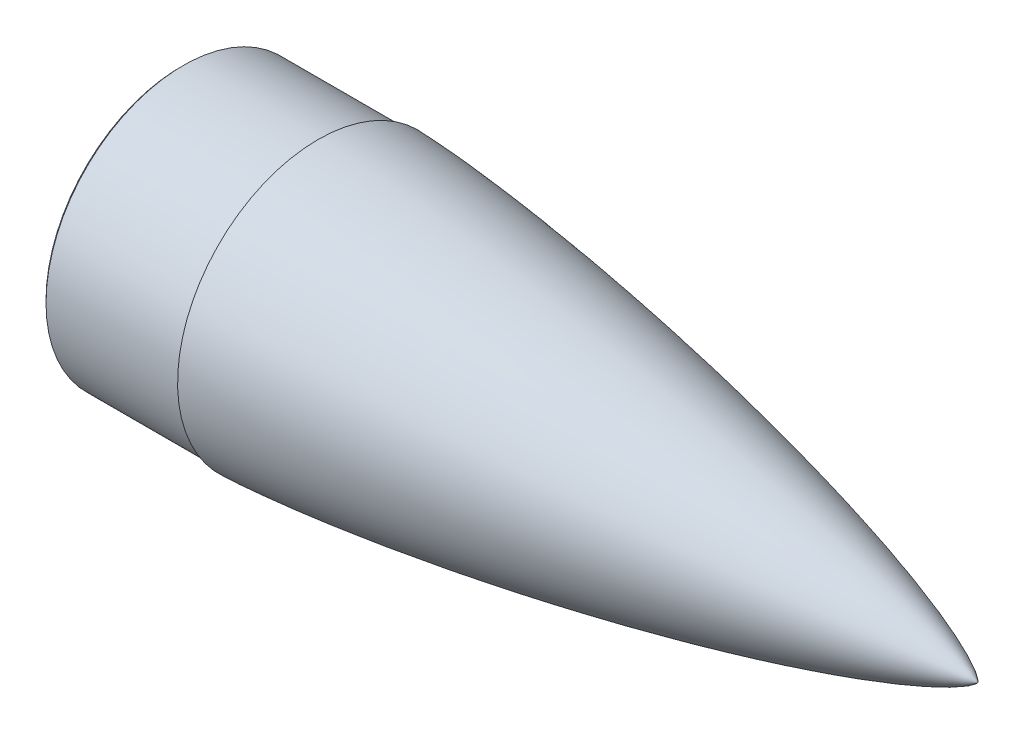
SolidWorks part; units mm, degrees
material "ABS"
ref_plane "Front Plane" through (0, 0, 0) normal (0, 0, 1) x (1, 0, 0)
ref_plane "Top Plane" through (0, 0, 0) normal (0, 1, 0) x (1, 0, 0)
ref_plane "Right Plane" through (0, 0, 0) normal (1, 0, 0) x (0, 0, -1)
ref_axis "Axis1" through (433.6458, 0, 0) along (-1, 0, 0)
sketch "Sketch10" plane through (0, 0, 0) normal (0, 0, 1) x (1, 0, 0)
  line L1 (-1.0327, 0) -> (486.9547, 0) construction
  line L3 (11.1125, 81.9998) -> (-84.6045, 81.9998)
  line L4 (408.9673, 0) -> (368.9673, 0)
  line L5 (-84.6045, 81.9998) -> (-84.6045, 84.9998)
  line L6 (-84.6045, 84.9998) -> (0.3953, 84.9998)
  line L7 (0.3953, 84.9998) -> (0.3953, 86.9998)
  spline S0 degree 4 poles (408.9673, 0) (408.9649, 0.0135) (408.958, 0.0399) (408.9365, 0.0905) (408.8922, 0.1741) (408.8263, 0.2756) (408.7217, 0.4158) (408.5611, 0.6051) (408.3056, 0.8724) (407.8697, 1.2753) (407.121, 1.8851) (405.8038, 2.8259) (403.4624, 4.2872) (399.3253, 6.5318) (392.4811, 9.7589) (380.6621, 14.628) (363.6372, 20.7117) (342.2152, 27.4765) (317.4285, 34.4976) (291.8793, 41.1048) (266.2105, 47.229) (240.4455, 52.9334) (214.5989, 58.2554) (188.6809, 63.2176) (165.9462, 67.2533) (146.422, 70.4938) (130.1279, 73.0449) (117.0786, 74.9942) (104.0155, 76.8485) (92.5733, 78.3845) (82.7571, 79.6356) (74.5713, 80.6322) (68.0193, 81.4008) (61.4637, 82.1394) (54.9047, 82.8464) (48.3422, 83.5199) (41.7761, 84.1578) (36.0275, 84.6822) (31.0979, 85.1052) (26.9883, 85.4387) (23.6997, 85.6932) (20.0858, 85.9584) (16.7199, 86.189) (13.6021, 86.387) (10.7327, 86.5546) (8.4366, 86.6787) (6.14, 86.7922) (4.1299, 86.8793) (2.4065, 86.9446) (1.2573, 86.979) (0.6827, 86.9949) (0.3953, 86.9998) knots 0 0 0 0 0 0.00013 0.00026 0.00052 0.0009 0.00128 0.001925 0.002882 0.004418 0.006927 0.011111 0.018279 0.030673 0.051704 0.083102 0.139909 0.202703 0.265496 0.32829 0.391083 0.453877 0.516671 0.579464 0.642258 0.673655 0.705051 0.736448 0.767845 0.799242 0.81494 0.830639 0.846337 0.862036 0.877734 0.893432 0.909131 0.924829 0.932678 0.940527 0.948377 0.956226 0.967169 0.972641 0.978113 0.983585 0.989056 0.994528 0.997264 1 1 1 1 1 construction
  spline S1 degree 4 poles (408.9673, 0) (408.9649, 0.0135) (408.958, 0.0399) (408.9365, 0.0905) (408.8922, 0.1741) (408.8263, 0.2756) (408.7217, 0.4158) (408.5611, 0.6051) (408.3056, 0.8724) (407.8697, 1.2753) (407.121, 1.8851) (405.8038, 2.8259) (403.4624, 4.2872) (399.3253, 6.5318) (392.4811, 9.7589) (380.6621, 14.628) (363.6372, 20.7117) (342.2152, 27.4765) (317.4285, 34.4976) (291.8793, 41.1048) (266.2105, 47.229) (240.4455, 52.9334) (214.5989, 58.2554) (188.6809, 63.2176) (165.9462, 67.2533) (146.422, 70.4938) (130.1279, 73.0449) (117.0786, 74.9942) (104.0155, 76.8485) (92.5733, 78.3845) (82.7571, 79.6356) (74.5713, 80.6322) (68.0193, 81.4008) (61.4637, 82.1394) (54.9047, 82.8464) (48.3422, 83.5199) (41.7761, 84.1578) (36.0275, 84.6822) (31.0979, 85.1052) (26.9883, 85.4387) (23.6997, 85.6932) (20.0858, 85.9584) (16.7199, 86.189) (13.6021, 86.387) (10.7327, 86.5546) (8.4366, 86.6787) (6.14, 86.7922) (4.1299, 86.8793) (2.4065, 86.9446) (1.2573, 86.979) (0.6827, 86.9949) (0.3953, 86.9998) knots 0 0 0 0 0 0.00013 0.00026 0.00052 0.0009 0.00128 0.001925 0.002882 0.004418 0.006927 0.011111 0.018279 0.030673 0.051704 0.083102 0.139909 0.202703 0.265496 0.32829 0.391083 0.453877 0.516671 0.579464 0.642258 0.673655 0.705051 0.736448 0.767845 0.799242 0.81494 0.830639 0.846337 0.862036 0.877734 0.893432 0.909131 0.924829 0.932678 0.940527 0.948377 0.956226 0.967169 0.972641 0.978113 0.983585 0.989056 0.994528 0.997264 1 1 1 1 1
  spline S2 degree 4 poles (368.9673, 0) (368.9653, 0.0123) (368.9594, 0.0365) (368.9406, 0.083) (368.9023, 0.1587) (368.8455, 0.2503) (368.7557, 0.3766) (368.6167, 0.5484) (368.3929, 0.7936) (368.0087, 1.1649) (367.3447, 1.7299) (366.1761, 2.6016) (364.0928, 3.96) (360.426, 6.0407) (354.4022, 9.0183) (344.043, 13.5077) (329.152, 19.1285) (310.4252, 25.3986) (288.7413, 31.9337) (266.3785, 38.1061) (243.9014, 43.8469) (221.332, 49.212) (198.684, 54.2345) (175.9669, 58.9343) (156.0346, 62.7717) (138.9133, 65.8645) (124.6221, 68.3077) (113.1754, 70.1797) (101.7151, 71.9664) (91.6754, 73.4517) (83.0615, 74.6659) (75.8775, 75.6363) (70.1269, 76.3867) (64.3728, 77.1101) (58.6152, 77.8049) (52.854, 78.4695) (47.0892, 79.1019) (42.0417, 79.6247) (37.7129, 80.0488) (34.1039, 80.385) (31.2157, 80.6428) (28.0648, 80.911) (24.6507, 81.1843) (21.4654, 81.4195) (18.5093, 81.6177) (16.0448, 81.767) (14.3191, 81.8612) (12.8395, 81.9336) (11.8527, 81.9739) (11.3593, 81.993) (11.1125, 81.9998) knots 0 0 0 0 0 0.000135 0.00027 0.00054 0.00092 0.001299 0.001947 0.002931 0.004512 0.007081 0.01138 0.018708 0.031424 0.052705 0.084103 0.14091 0.203703 0.266497 0.329291 0.392084 0.454878 0.517672 0.580465 0.643259 0.674656 0.706052 0.737449 0.768846 0.800243 0.815941 0.831639 0.847338 0.863036 0.878735 0.894433 0.910132 0.92583 0.933679 0.941528 0.949378 0.957227 0.96792 0.978613 0.98396 0.989307 0.994653 0.997327 1 1 1 1 1 construction
  spline S3 degree 4 poles (368.9673, 0) (368.9653, 0.0123) (368.9594, 0.0365) (368.9406, 0.083) (368.9023, 0.1587) (368.8455, 0.2503) (368.7557, 0.3766) (368.6167, 0.5484) (368.3929, 0.7936) (368.0087, 1.1649) (367.3447, 1.7299) (366.1761, 2.6016) (364.0928, 3.96) (360.426, 6.0407) (354.4022, 9.0183) (344.043, 13.5077) (329.152, 19.1285) (310.4252, 25.3986) (288.7413, 31.9337) (266.3785, 38.1061) (243.9014, 43.8469) (221.332, 49.212) (198.684, 54.2345) (175.9669, 58.9343) (156.0346, 62.7717) (138.9133, 65.8645) (124.6221, 68.3077) (113.1754, 70.1797) (101.7151, 71.9664) (91.6754, 73.4517) (83.0615, 74.6659) (75.8775, 75.6363) (70.1269, 76.3867) (64.3728, 77.1101) (58.6152, 77.8049) (52.854, 78.4695) (47.0892, 79.1019) (42.0417, 79.6247) (37.7129, 80.0488) (34.1039, 80.385) (31.2157, 80.6428) (28.0648, 80.911) (24.6507, 81.1843) (21.4654, 81.4195) (18.5093, 81.6177) (16.0448, 81.767) (14.3191, 81.8612) (12.8395, 81.9336) (11.8527, 81.9739) (11.3593, 81.993) (11.1125, 81.9998) knots 0 0 0 0 0 0.000135 0.00027 0.00054 0.00092 0.001299 0.001947 0.002931 0.004512 0.007081 0.01138 0.018708 0.031424 0.052705 0.084103 0.14091 0.203703 0.266497 0.329291 0.392084 0.454878 0.517672 0.580465 0.643259 0.674656 0.706052 0.737449 0.768846 0.800243 0.815941 0.831639 0.847338 0.863036 0.878735 0.894433 0.910132 0.92583 0.933679 0.941528 0.949378 0.957227 0.96792 0.978613 0.98396 0.989307 0.994653 0.997327 1 1 1 1 1
  dimension "D4" = 84.9998
  dimension "D1" = 86.9998
  dimension "D3" = 410
  dimension "D5" = 370
  dimension "D6" = 84.9998
  dimension "D2" = 3
revolve "Revolve1" add sketch "Sketch10" angle 360 about axis through (433.6458, 0, 0) along (-1, 0, 0)
chamfer "Chamfer1" distance 1.5 angle 45 1 edges at (-84.6045, 0, -84.9998)
equation "\"TubeDiameter\" = 6.6929in"
equation "\"D1@Sketch10\"=(\"TubeDiameter\"/2)+2mm"
equation "\"D6@Sketch10\"=\"TubeDiameter\"/2"
